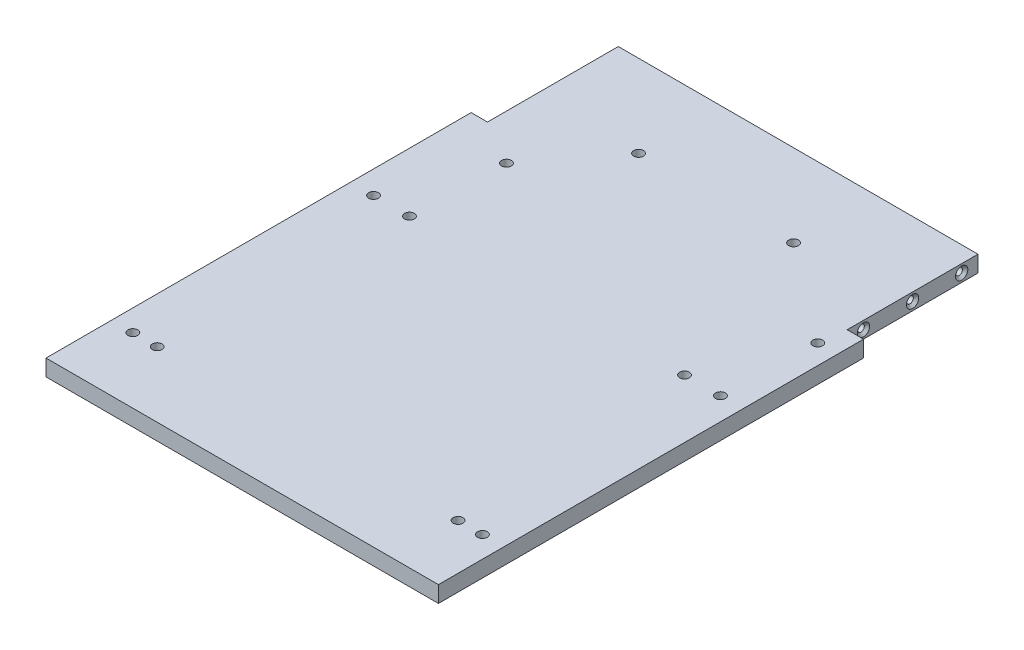
SolidWorks part; units mm, degrees
ref_plane "Front Plane" through (0, 0, 0) normal (0, 0, 1) x (1, 0, 0)
ref_plane "Top Plane" through (0, 0, 0) normal (0, 1, 0) x (1, 0, 0)
ref_plane "Right Plane" through (0, 0, 0) normal (1, 0, 0) x (0, 0, -1)
sketch "Sketch1" plane through (0, 0, 0) normal (0, 1, 0) x (1, 0, 0)
  line L0 (-6.35, 0) -> (-6.35, -50.8)
  line L1 (-6.35, 0) -> (-146.05, 0)
  line L2 (0, -50.8) -> (0, -215.9)
  line L3 (0, -215.9) -> (-152.4, -215.9)
  line L4 (-152.4, -50.8) -> (-152.4, -215.9)
  line L5 (-6.35, -50.8) -> (0, -50.8)
  line L6 (-146.05, 0) -> (-146.05, -50.8)
  line L7 (-146.05, -50.8) -> (-152.4, -50.8)
  point P7 (-3.175, -50.8)
  dimension "D1" = 152.4
  dimension "D2" = 215.9
  dimension "D3" = 50.8
  dimension "D4" = 6.35
  dimension "D5" = 6.35
  dimension "D6" = 50.8
extrude "Boss-Extrude1" add sketch "Sketch1" along normal blind 6.35
sketch "Sketch2" plane through (-6.35, 0, 0) normal (1, 0, 0) x (0, 0, -1)
  line L0 (-50.8, 6.35) -> (-50.8, 0) construction
  line L1 (-50.8, 6.35) -> (-50.8, 0) construction
  line L2 (-50.8, 0) -> (0, 0) construction
  circle A0 centre (-44.45, 3.175) radius 1.8288
  circle A1 centre (-25.4, 3.175) radius 1.8288
  circle A2 centre (-6.35, 3.175) radius 1.8288
  dimension "D4" = 3.175
  dimension "D5" = 3.175
  dimension "D6" = 3.6576
  dimension "D7" = 3.6576
  dimension "D8" = 3.6576
  dimension "D1" = 6.35
  dimension "D2" = 25.4
  dimension "D3" = 44.45
hole_wizard "#6-32 Tapped Hole1" positions "Sketch3" profile "Sketch4" tap size "#6-32" standard "ANSI Inch"
sketch "Sketch3" plane through (-6.35, 0, 0) normal (1, 0, 0) x (0, 0, -1)
  point P0 (-44.45, 3.175)
  point P3 (-25.4, 3.175)
  point P6 (-6.35, 3.175)
sketch "Sketch4" plane through (-6.35, 3.175, 44.45) normal (0, 1, 0) x (0, 0, -1)
  line L0 (0, 0) -> (0, 12.7)
  line L1 (0, 12.7) -> (1.3525, 11.8873)
  line L2 (1.3525, 11.8873) -> (1.3525, 1.0351)
  line L3 (1.3525, 1.0351) -> (2.3876, 0)
  line L5 (2.3876, 0) -> (0, 0)
  line L6 (-1.3525, 1.0351) -> (-2.3876, 0) construction
  line L10 (0, 12.7) -> (-1.3526, 11.8873) construction
  line L11 (0, -6.35) -> (0, 107.95) construction
  dimension "Tap Drill Dia." = 2.7051
  dimension "Tap Drill Depth" = 12.7
  dimension "Near C'Sink Dia." = 4.7752
  dimension "Near C'Sink Angle" = 90
  dimension "Drill Angle" = 118
cosmetic thread "Hole Thread1" parameters "D1"=10.16, "D2"=3.5052
cosmetic thread "Hole Thread2" parameters "D1"=10.16, "D2"=3.5052
cosmetic thread "Hole Thread3" parameters "D1"=10.16, "D2"=3.5052
sketch "Sketch5" plane through (-146.05, 0, 0) normal (-1, 0, 0) x (0, 0, 1)
  circle A0 centre (6.35, 3.175) radius 1.8288
  circle A1 centre (25.4, 3.175) radius 1.8288
  circle A2 centre (44.45, 3.175) radius 1.8288
  dimension "D1" = 3.6576
  dimension "D2" = 3.6576
  dimension "D3" = 3.6576
hole_wizard "#6-32 Tapped Hole2" positions "Sketch6" profile "Sketch7" tap size "#6-32" standard "ANSI Inch"
sketch "Sketch6" plane through (-146.05, 0, 0) normal (-1, 0, 0) x (0, 0, 1)
  point P0 (6.35, 3.175)
  point P3 (25.4, 3.175)
  point P6 (44.45, 3.175)
sketch "Sketch7" plane through (-146.05, 3.175, 6.35) normal (0, 1, 0) x (0, 0, 1)
  line L0 (0, 0) -> (0, 12.7)
  line L1 (0, 12.7) -> (1.3525, 11.8873)
  line L2 (1.3525, 11.8873) -> (1.3525, 1.0351)
  line L3 (1.3525, 1.0351) -> (2.3876, 0)
  line L5 (2.3876, 0) -> (0, 0)
  line L6 (-1.3525, 1.0351) -> (-2.3876, 0) construction
  line L10 (0, 12.7) -> (-1.3526, 11.8873) construction
  line L11 (0, -6.35) -> (0, 107.95) construction
  dimension "Tap Drill Dia." = 2.7051
  dimension "Tap Drill Depth" = 12.7
  dimension "Near C'Sink Dia." = 4.7752
  dimension "Near C'Sink Angle" = 90
  dimension "Drill Angle" = 118
cosmetic thread "Hole Thread4" parameters "D1"=10.16, "D2"=3.5052
cosmetic thread "Hole Thread5" parameters "D1"=10.16, "D2"=3.5052
cosmetic thread "Hole Thread6" parameters "D1"=10.16, "D2"=3.5052
sketch "Sketch9" plane through (0, 6.35, 0) normal (0, 1, 0) x (1, 0, 0)
  line L0 (-152.4, -215.9) -> (0, -215.9) construction
  line L1 (-152.4, -50.8) -> (-152.4, -215.9) construction
  circle A0 centre (-134.62, -190.5) radius 1.8987
  circle A2 centre (-144.0739, -190.5) radius 1.8987
  dimension "D2" = 25.4
  dimension "D3" = 17.78
  dimension "D4" = 3.7973
  dimension "D6" = 3.7973
  dimension "D7" = 9.4539
  dimension "D8" = 25.4
sketch "Sketch16" plane through (0, 6.35, 0) normal (0, 1, 0) x (1, 0, 0)
  line L0 (-6.35, -50.8) -> (-6.35, 0) construction
  line L1 (-6.35, 0) -> (-146.05, 0) construction
  circle A0 centre (-45.974, -32.004) radius 1.8986
  circle A1 centre (-106.172, -32.004) radius 1.8987
  dimension "D1" = 39.624
  dimension "D2" = 32.004
  dimension "D3" = 60.198
  dimension "D4" = 32.004
  dimension "D5" = 3.7973
  dimension "D6" = 3.7973
sketch "Sketch20" plane through (0, 6.35, 0) normal (0, 1, 0) x (1, 0, 0)
  line L0 (0, -50.8) -> (-6.35, -50.8) construction
  line L1 (0, -215.9) -> (0, -50.8) construction
  line L2 (-146.05, -50.8) -> (-152.4, -50.8) construction
  line L4 (-152.4, -50.8) -> (-152.4, -215.9) construction
  circle A0 centre (-128.524, -60.96) radius 1.8987
  circle A1 centre (-129.54, -97.5981) radius 1.8987
  circle A2 centre (-143.4846, -97.6122) radius 1.8987
  circle A3 centre (-7.62, -60.96) radius 1.8987
  circle A4 centre (-22.7076, -97.6122) radius 1.8986
  circle A5 centre (-8.763, -97.6122) radius 1.8987
  dimension "D1" = 10.16
  dimension "D2" = 7.62
  dimension "D3" = 36.6522
  dimension "D4" = 8.763
  dimension "D5" = 13.9446
  dimension "D6" = 36.6522
  dimension "D7" = 3.7973
  dimension "D8" = 3.7973
  dimension "D9" = 3.7973
  dimension "D10" = 3.7973
  dimension "D11" = 3.7973
  dimension "D12" = 3.7973
  dimension "D13" = 10.16
  dimension "D14" = 36.6522
  dimension "D15" = 13.9446
  dimension "D16" = 36.6522
  dimension "D17" = 23.876
  dimension "D18" = 22.86
sketch "Sketch25" plane through (0, 6.35, 0) normal (0, 1, 0) x (1, 0, 0)
  line L0 (-152.4, -215.9) -> (0, -215.9) construction
  circle A0 centre (-8.3261, -190.5) radius 1.8987
  circle A3 centre (-17.78, -190.5) radius 1.8987
  dimension "D1" = 3.7973
  dimension "D2" = 9.4539
  dimension "D3" = 25.4
  dimension "D4" = 3.7973
extrude "Cut-Extrude1" cut sketch "Sketch25" against normal through all
extrude "Cut-Extrude2" cut sketch "Sketch20" against normal through all
extrude "Cut-Extrude3" cut sketch "Sketch16" against normal through all
extrude "Cut-Extrude4" cut sketch "Sketch9" against normal through all
